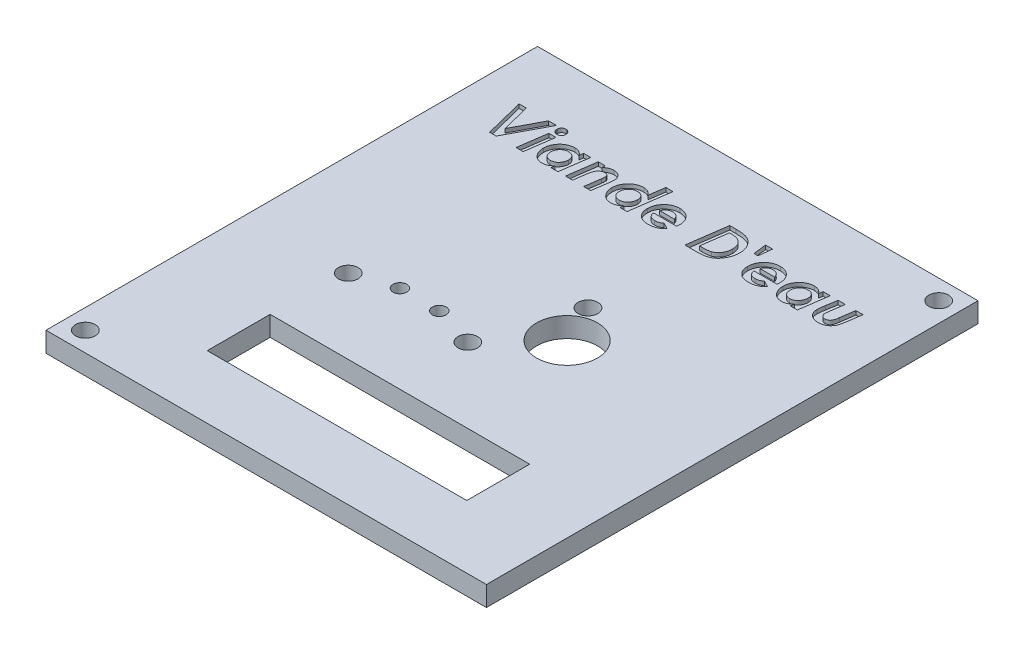
SolidWorks part; units mm, degrees
ref_plane "Front Plane" through (0, 0, 0) normal (0, 0, 1) x (1, 0, 0)
ref_plane "Top Plane" through (0, 0, 0) normal (0, 1, 0) x (1, 0, 0)
ref_plane "Right Plane" through (0, 0, 0) normal (1, 0, 0) x (0, 0, -1)
sketch "Sketch1" plane through (0, 0, 0) normal (0, 1, 0) x (1, 0, 0)
  line L1 (-56, -62.5) -> (56, -62.5)
  line L2 (-56, -62.5) -> (-56, 62.5)
  line L3 (-56, 62.5) -> (56, 62.5)
  line L4 (56, -62.5) -> (56, 62.5)
  line L5 (-56, -62.5) -> (56, 62.5) construction
  line L6 (-56, 62.5) -> (56, -62.5) construction
  point P0 (0, 0)
  dimension "D1" = 112
  dimension "D2" = 125
extrude "Boss-Extrude1" add sketch "Sketch1" along normal blind 5.08
sketch "Sketch5" plane through (0, 5.08, 0) normal (0, 1, 0) x (1, 0, 0)
  line L0 (-56, -62.5) -> (56, -62.5) construction
  line L1 (-31, -46.5) -> (35, -46.5)
  line L2 (-31, -46.5) -> (-31, -30.5)
  line L3 (-31, -30.5) -> (35, -30.5)
  line L4 (35, -46.5) -> (35, -30.5)
  line L5 (-31, -46.5) -> (35, -30.5) construction
  line L6 (-31, -30.5) -> (35, -46.5) construction
  line L10 (-56, 62.5) -> (-56, -62.5) construction
  circle A0 centre (12.5, 1.5) radius 7.75
  circle A1 centre (-30.13, -11.51) radius 2.5
  circle A2 centre (-20.25, -8.2495) radius 1.75
  circle A3 centre (-10.25, -8.2495) radius 1.75
  circle A4 centre (0.2695, -11.51) radius 2.5
  circle A5 centre (8.001, 11.311) radius 2.5
  point P0 (2, -38.5)
  dimension "D4" = 15.5
  dimension "D8" = 5
  dimension "D9" = 3.5
  dimension "D5" = 47.999
  dimension "D6" = 51.189
  dimension "D10" = 43.5
  dimension "D12" = 55.7305
  dimension "D13" = 74.01
  dimension "D14" = 66.25
  dimension "D15" = 70.7495
  dimension "D16" = 70.7495
  dimension "D17" = 76.25
  dimension "D18" = 86.13
  dimension "D19" = 74.01
  dimension "D1" = 66
  dimension "D2" = 16
  dimension "D3" = 16
  dimension "D7" = 25
  dimension "D11" = 61
extrude "Cut-Extrude1" cut sketch "Sketch5" against normal up to next contours A0 | A4 | A3 | A2 | A1 | L1 L4 L3 L2 | A5 region at (2, 5.08, 38.5) region at (12.5, 5.08, -1.5) region at (-30.13, 5.08, 11.51) region at (-20.25, 5.08, 8.2495) region at (-10.25, 5.08, 8.2495) region at (0.2695, 5.08, 11.51) region at (8.001, 5.08, -11.311)
sketch "Sketch7" plane through (0, 5.08, 0) normal (0, 1, 0) x (1, 0, 0)
  line L5 (56, 62.5) -> (-56, 62.5) construction
  line L6 (56, -62.5) -> (56, 62.5) construction
  line L7 (-56, -62.5) -> (56, -62.5) construction
  line L8 (-56, 62.5) -> (-56, -62.5) construction
  circle A0 centre (-51, -57.5) radius 2.5
  circle A1 centre (51, 57.5) radius 2.5
  dimension "D2" = 5
  dimension "D4" = 5
  dimension "D3" = 5
  dimension "D5" = 5
  dimension "D6" = 5
extrude "Cut-Extrude3" cut sketch "Sketch7" against normal blind 4
sketch "Sketch8" plane through (0, 5.08, 0) normal (0, 1, 0) x (1, 0, 0)
  line L0 (-56, 37.5) -> (56, 37.5) construction
  line L1 (56, 62.5) -> (-56, 62.5) construction
  line L2 (-56, 62.5) -> (-56, -62.5) construction
  text T0 "<b><i>Viande D'eau</i></b>" font "Century Gothic" height 10
  point P1 (0, 37.5)
  point P7 (0, 62.5)
  dimension "D1" = 25
extrude "Cut-Extrude4" cut sketch "Sketch8" against normal blind 1
